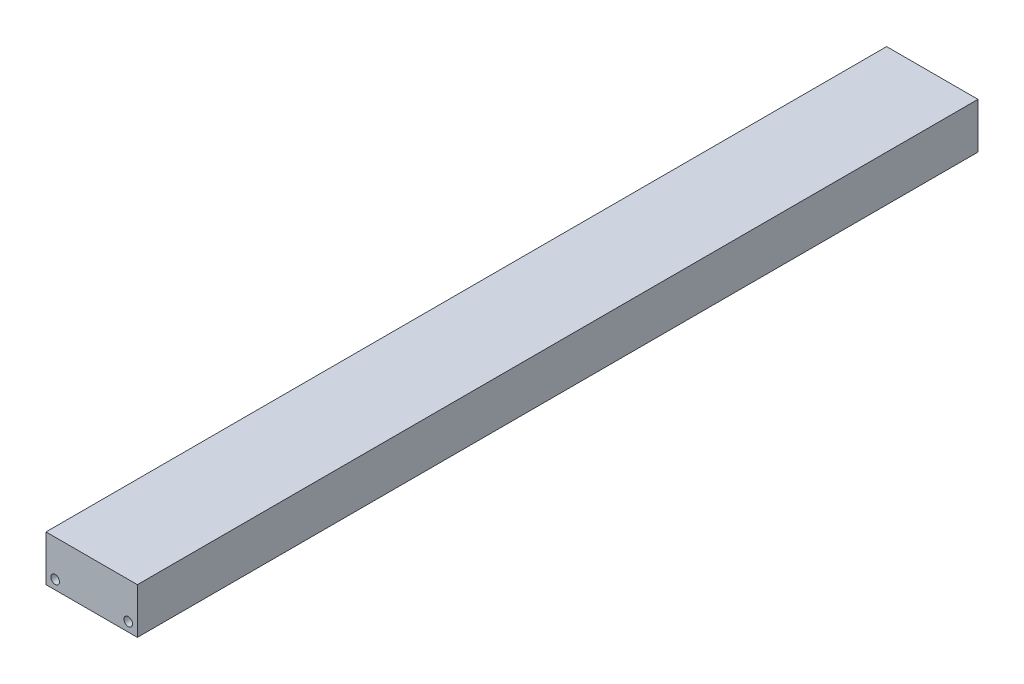
SolidWorks part; units mm, degrees
ref_plane "Front Plane" through (0, 0, 0) normal (0, 0, 1) x (1, 0, 0)
ref_plane "Top Plane" through (0, 0, 0) normal (0, 1, 0) x (1, 0, 0)
ref_plane "Right Plane" through (0, 0, 0) normal (1, 0, 0) x (0, 0, -1)
sketch "Sketch1" plane through (0, 0, 0) normal (0, 0, 1) x (1, 0, 0)
  line L0 (0, 31.75) -> (0, -31.75) construction
  line L1 (-31.75, -31.75) -> (31.75, -31.75)
  line L2 (-31.75, -31.75) -> (-31.75, 31.75)
  line L3 (-31.75, 31.75) -> (31.75, 31.75)
  line L4 (31.75, -31.75) -> (31.75, 31.75)
  line L5 (-31.75, -31.75) -> (31.75, 31.75) construction
  line L6 (-31.75, 31.75) -> (31.75, -31.75) construction
  line L7 (-31.75, 0) -> (31.75, 0) construction
  circle A0 centre (-25.4, 25.4) radius 3
  circle A1 centre (25.4, -25.4) radius 3
  circle A2 centre (-25.4, -25.4) radius 3
  circle A3 centre (25.4, 25.4) radius 3
  point P0 (0, 0)
  point P22 (8.4874, -9.3553)
  dimension "D3" = 6
  dimension "D9" = 50.8
  dimension "D4" = 50.8
  dimension "D1" = 63.5
  dimension "D2" = 63.5
  dimension "D5" = 6.35
extrude "Boss-Extrude1" add sketch "Sketch1" along normal mid plane 584.2
sketch "Sketch3" plane through (0, 0, 292.1) normal (0, 0, 1) x (1, 0, 0)
  line L0 (31.75, -31.75) -> (31.75, 31.75) construction
  line L1 (-31.75, 31.75) -> (31.75, 31.75)
  line L2 (-31.75, 31.75) -> (-31.75, 0)
  line L3 (-31.75, 0) -> (31.75, 0)
  line L4 (31.75, 31.75) -> (31.75, 0)
extrude "Cut-Extrude2" cut sketch "Sketch3" against normal through all
